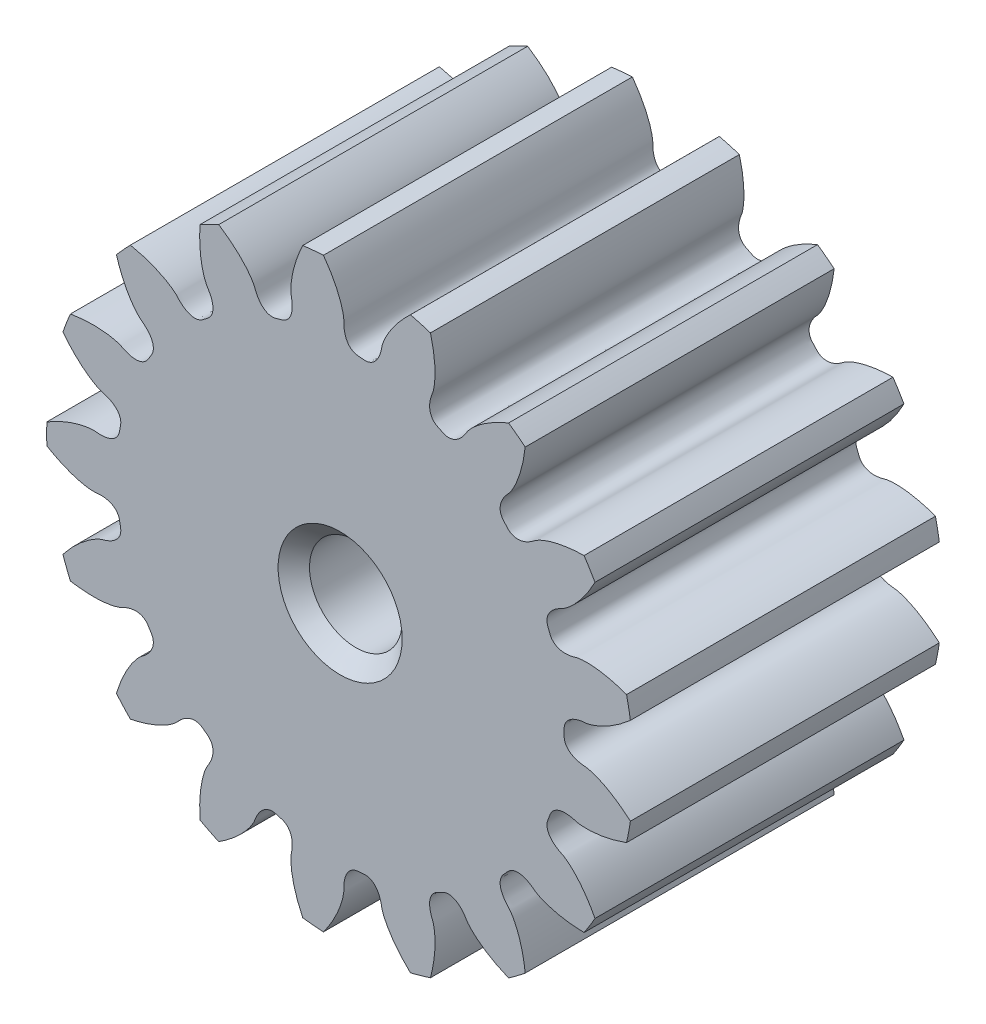
SolidWorks part; units mm, degrees
ref_plane "Front" through (0, 0, 0) normal (0, 0, 1) x (1, 0, 0)
ref_plane "Top" through (0, 0, 0) normal (0, 1, 0) x (1, 0, 0)
ref_plane "Right" through (0, 0, 0) normal (1, 0, 0) x (0, 0, -1)
ref_axis "Ось1" through (0, 0, 50) along (0, 0, -1)
sketch "SketchRevolveSun_Driver01" plane through (0, 0, 0) normal (1, 0, 0) x (0, 0, -1)
  line L0 (0, 0) -> (1, 0) construction
  line L1 (-2.5, 0) -> (-2.5, 4.75)
  line L2 (-2.5, 4.75) -> (2.5, 4.75)
  line L3 (2.5, 4.75) -> (2.5, 0)
  line L4 (2.5, 0) -> (-2.5, 0)
  dimension "Side1" = 2.5
  dimension "OutsideRadius" = 4.75
  dimension "Side2" = 2.5
revolve "Sun_Driver01" add sketch "SketchRevolveSun_Driver01" angle 360 about L0
sketch "SketchToothSun_Driver01" plane through (0, 0, 0) normal (0, 0, 1) x (1, 0, 0)
  arc A0 (4.7194, 0.7265) -> (4.7194, -0.7265) centre (0, 0) cw
  spline S0 degree 3 poles (4.7194, -0.7265) (4.679, -0.6901) (4.6184, -0.6389) (4.5366, -0.5765) (4.4789, -0.5354) (4.4235, -0.4986) (4.3706, -0.466) (4.3204, -0.4372) (4.273, -0.412) (4.2287, -0.3904) (4.1876, -0.3719) (4.1499, -0.3564) (4.1158, -0.3437) (4.0853, -0.3334) (4.0586, -0.3254) (4.0358, -0.3194) (4.017, -0.315) (4.0022, -0.3121) (3.9689, -0.3067) (3.9312, -0.3056) (3.8893, -0.2982) (3.864, -0.2928) (3.8397, -0.2865) (3.8162, -0.2791) (3.7936, -0.2706) (3.7717, -0.2609) (3.7506, -0.2499) (3.7302, -0.2373) (3.7105, -0.2228) (3.6915, -0.2061) (3.6736, -0.1867) (3.6571, -0.1642) (3.6429, -0.1383) (3.6319, -0.1089) (3.6262, -0.0794) (3.6237, -0.0428) (3.6258, 0) (3.6237, 0.0428) (3.6262, 0.0794) (3.6319, 0.1089) (3.6429, 0.1383) (3.6571, 0.1642) (3.6736, 0.1867) (3.6915, 0.2061) (3.7105, 0.2228) (3.7302, 0.2373) (3.7506, 0.2499) (3.7717, 0.2609) (3.7936, 0.2706) (3.8162, 0.2791) (3.8397, 0.2865) (3.864, 0.2928) (3.8893, 0.2982) (3.9312, 0.3056) (3.9689, 0.3067) (4.0022, 0.3121) (4.017, 0.315) (4.0358, 0.3194) (4.0586, 0.3254) (4.0853, 0.3334) (4.1158, 0.3437) (4.1499, 0.3564) (4.1876, 0.3719) (4.2287, 0.3904) (4.273, 0.412) (4.3204, 0.4372) (4.3706, 0.466) (4.4235, 0.4986) (4.4789, 0.5354) (4.5366, 0.5765) (4.6184, 0.6389) (4.679, 0.6901) (4.7194, 0.7265) knots 0 0 0 0 0.058365 0.085243 0.110586 0.134392 0.156663 0.177398 0.196597 0.21426 0.230387 0.244978 0.258033 0.269552 0.279536 0.287983 0.294895 0.300271 0.30411 0.331114 0.340625 0.349862 0.358855 0.367643 0.376273 0.384801 0.3933 0.401854 0.410565 0.419553 0.428946 0.438871 0.449424 0.460632 0.472413 0.481614 0.5 0.518386 0.527587 0.539368 0.550576 0.561129 0.571054 0.580447 0.589435 0.598146 0.6067 0.615199 0.623727 0.632357 0.641145 0.650138 0.659375 0.668886 0.69589 0.699729 0.705105 0.712017 0.720464 0.730448 0.741967 0.755022 0.769613 0.78574 0.803403 0.822602 0.843337 0.865608 0.889414 0.914757 0.941635 1 1 1 1
extrude "ToothExtrudeCutSun_Driver01" cut sketch "SketchToothSun_Driver01" against normal blind 2.5 and the other way blind 2.5
ref_axis "Ось2" through (80.9, 0, 0) along (-1, 0, 0)
ref_plane "Плоскость1" through (0, 0, 0) normal (0, 0, -1) x (1, 0, 0)
pattern_circular "PatternSun_Driver01" count 17 every 21.176 about axis through (0, 0, 50) along (0, 0, -1) of "ToothExtrudeCutSun_Driver01"
sketch "BoreRevolveSketch" plane through (0, 0, 0) normal (1, 0, 0) x (0, 0, -1)
  line L0 (0, 0) -> (1, 0) construction
  line L1 (-2.5, 0) -> (2.5, 0)
  line L2 (2.5, 0) -> (2.5, 1.004)
  line L3 (2.5, 1.004) -> (2.246, 0.75)
  line L4 (2.246, 0.75) -> (-2.246, 0.75)
  line L5 (-2.246, 0.75) -> (-2.5, 1.004)
  line L6 (-2.5, 1.004) -> (-2.5, 0)
  dimension "BoreSide1" = 2.5
  dimension "TaperSide1" = 1.004
  dimension "Chamfer1X" = 0.254
  dimension "Chamfer1Y" = 0.254
  dimension "BoreSide2" = 2.5
  dimension "TaperSide2" = 1.004
revolve "BoreRevolveCut" cut sketch "BoreRevolveSketch" angle 360 about L0
sketch "AuxiliarySketchSun_Driver01" plane through (0, 0, 0) normal (0, 0, 1) x (1, 0, 0)
  circle A0 centre (0, 0) radius 4.25 construction
  circle A1 centre (0, 0) radius 3.9937 construction
  circle A2 centre (0, 0) radius 3.9946 construction
  circle A3 centre (0, 0) radius 4.75 construction
  circle A4 centre (0, 0) radius 3.625 construction
  dimension "PitchDiameter" = 8.5
  dimension "BaseDiameter" = 7.9874
  dimension "FormDiameter" = 7.9892
  dimension "MajorDiameter" = 9.5
  dimension "MinorDiameter" = 7.25
